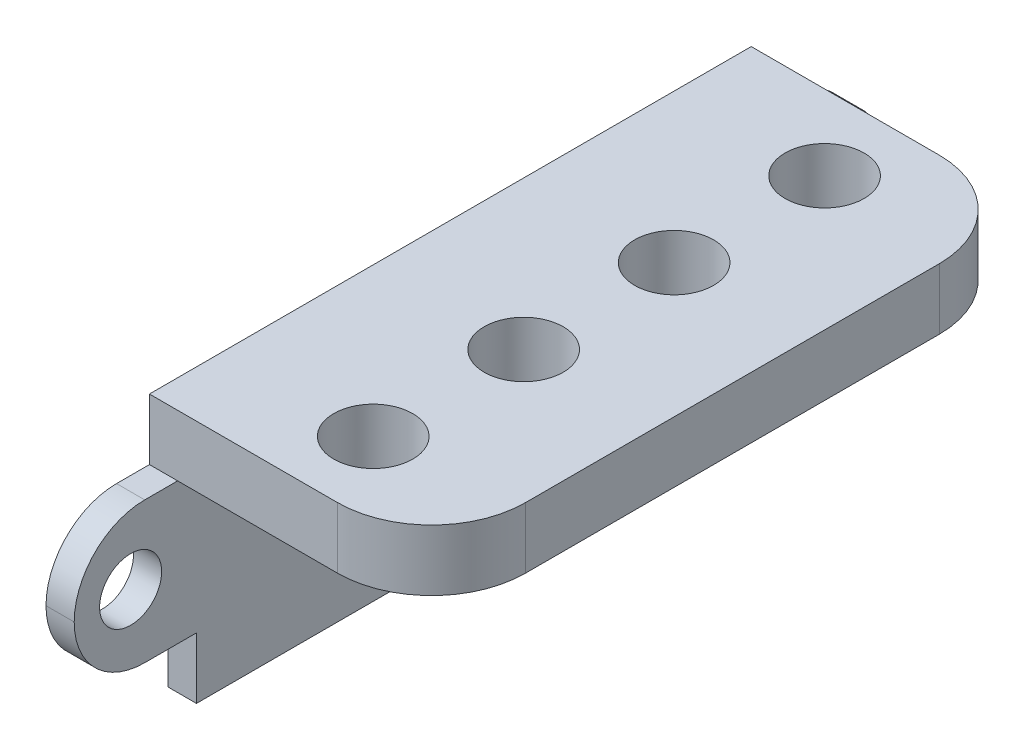
SolidWorks part; units mm, degrees
ref_plane "前基準面" through (0, 0, 0) normal (0, 0, 1) x (1, 0, 0)
ref_plane "上基準面" through (0, 0, 0) normal (0, 1, 0) x (1, 0, 0)
ref_plane "右基準面" through (0, 0, 0) normal (1, 0, 0) x (0, 0, -1)
sketch "草圖1" plane through (0, 0, 0) normal (1, 0, 0) x (0, 0, -1)
  line L1 (-21.5, 3.75) -> (21.5, 3.75)
  line L2 (-21.5, 3.75) -> (-21.5, -3.75)
  line L3 (-21.5, -3.75) -> (21.5, -3.75)
  line L4 (21.5, 3.75) -> (21.5, -3.75)
  line L5 (-21.5, 3.75) -> (21.5, -3.75) construction
  line L6 (-21.5, -3.75) -> (21.5, 3.75) construction
  point P0 (0, 0)
  dimension "D1" = 43
  dimension "D2" = 7.5
extrude "填料-伸長1" add sketch "草圖1" along normal blind 1.5
sketch "草圖2" plane through (1.5, 0, 0) normal (1, 0, 0) x (0, 0, -1)
  circle A2 centre (-18.5, 0) radius 1.65
  circle A3 centre (18.5, 0) radius 1.65
  dimension "D1" = 37
  dimension "D2" = 18.5
  dimension "D3" = 3.3
  dimension "D4" = 3.3
extrude "除料-伸長2" cut sketch "草圖2" against normal blind 11.5
fillet "圓角1" radius 3.75 4 edges at (0.75, -3.75, -21.5) (0.75, 3.75, -21.5) (0.75, -3.75, 21.5) (0.75, 3.75, 21.5)
sketch "草圖3" plane through (0, 0, 0) normal (-1, 0, 0) x (0, 0, 1)
  line L1 (15, -7) -> (-15, -7)
  line L2 (15, -7) -> (15, 7)
  line L3 (15, 7) -> (-15, 7)
  line L4 (-15, -7) -> (-15, 7)
  line L5 (15, -7) -> (-15, 7) construction
  line L6 (15, 7) -> (-15, -7) construction
  point P0 (0, 0)
  dimension "D1" = 14
  dimension "D2" = 30
extrude "填料-伸長3" add sketch "草圖3" against normal up to vertex (1.5 mm away) up to point (1.5, 3.75, 17.75)
sketch "草圖4" plane through (0, 7, 0) normal (0, 1, 0) x (1, 0, 0)
  line L1 (0, 16) -> (15, 16)
  line L2 (0, 16) -> (0, -16)
  line L3 (0, -16) -> (15, -16)
  line L4 (15, 16) -> (15, -16)
  line L5 (0, 15) -> (0, -15) construction
  line L6 (1.5, -17.75) -> (0, -17.75) construction
  dimension "D1" = 15
  dimension "D2" = 32
  dimension "D3" = 16
extrude "填料-伸長4" add sketch "草圖4" against normal up to vertex (3.25 mm away) up to point (0, 3.75, 15)
sketch "草圖5" plane through (0, 3.75, 0) normal (0, -1, 0) x (1, 0, 0)
  line L0 (1.5, 16) -> (15, 16) construction
  line L1 (1.5, -16) -> (1.5, 16) construction
  circle A0 centre (7.9, 12) radius 2.1
  circle A1 centre (7.9, 4) radius 2.1
  circle A2 centre (7.9, -4) radius 2.1
  circle A3 centre (7.9, -12) radius 2.1
  dimension "D1" = 4
  dimension "D3" = 4.2
  dimension "D2" = 6.4
  dimension "D4" = 4
extrude "除料-伸長3" cut sketch "草圖5" against normal blind 13
fillet "圓角3" radius 5 2 edges at (15, 5.375, -16) (15, 5.375, 16)
